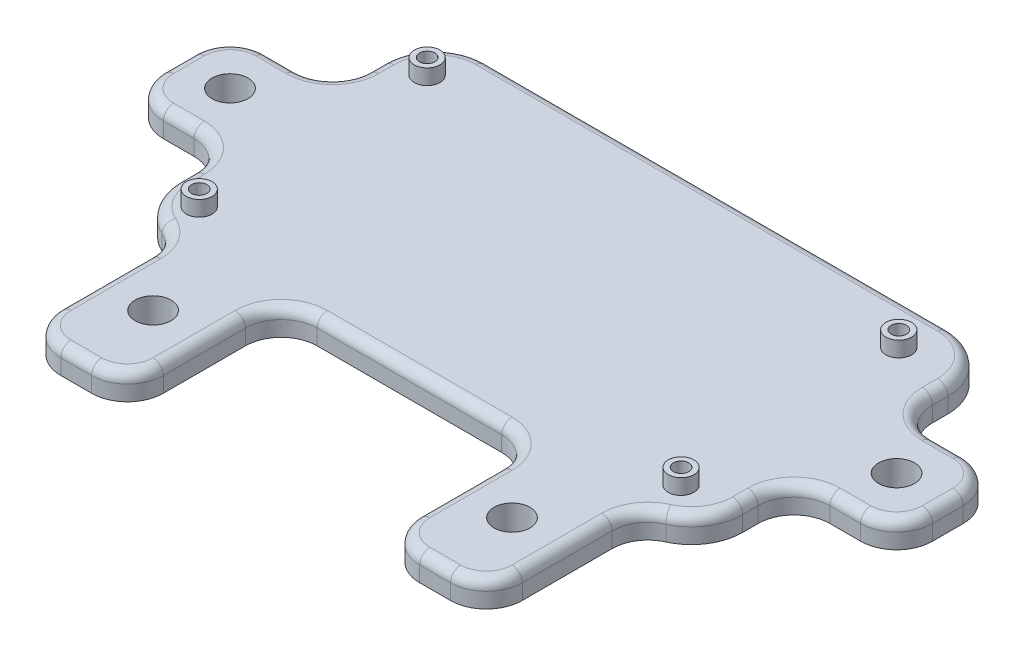
SolidWorks part; units mm, degrees
ref_plane "Front Plane" through (0, 0, 0) normal (0, 0, 1) x (1, 0, 0)
ref_plane "Top Plane" through (0, 0, 0) normal (0, 1, 0) x (1, 0, 0)
ref_plane "Right Plane" through (0, 0, 0) normal (1, 0, 0) x (0, 0, -1)
sketch "Sketch1" plane through (0, 0, 0) normal (0, 1, 0) x (1, 0, 0)
  line L1 (-49.43, 40.0745) -> (60.57, 40.0745)
  line L2 (-49.43, 40.0745) -> (-49.43, -19.9255)
  line L3 (-49.43, -19.9255) -> (60.57, -19.9255)
  line L4 (60.57, 40.0745) -> (60.57, -19.9255)
  dimension "D1" = 60
  dimension "D2" = 110
extrude "Boss-Extrude1" add sketch "Sketch1" along normal blind 5
sketch "Sketch2" plane through (0, 5, 0) normal (0, 1, 0) x (1, 0, 0)
  line L0 (-49.43, -19.9255) -> (60.57, -19.9255) construction
  line L1 (-49.43, 40.0745) -> (-49.43, -19.9255) construction
  circle A0 centre (-42.43, 31.5245) radius 1.0922
  circle A1 centre (-42.43, -12.9255) radius 1.0922
  circle A2 centre (51.55, -12.9255) radius 1.0922
  circle A3 centre (49.55, 31.5245) radius 1.0922
  dimension "D4" = 2.1844
  dimension "D5" = 93.98
  dimension "D1" = 44.45
  dimension "D2" = 7
  dimension "D3" = 7
extrude "Cut-Extrude1" cut sketch "Sketch2" against normal blind 10
sketch "Sketch3" plane through (0, 5, 0) normal (0, 1, 0) x (1, 0, 0)
  circle A0 centre (-42.43, 31.5245) radius 2.5
  circle A1 centre (-42.43, -12.9255) radius 2.5
  circle A2 centre (51.55, -12.9255) radius 2.5
  circle A3 centre (49.55, 31.5245) radius 2.5
  dimension "D1" = 5
extrude "Boss-Extrude2" add sketch "Sketch3" along normal blind 3
sketch "Sketch4" plane through (0, 8, 0) normal (0, 1, 0) x (1, 0, 0)
  circle A0 centre (-42.43, 31.5245) radius 1.5
  circle A1 centre (49.55, 31.5245) radius 1.5
  circle A2 centre (51.55, -12.9255) radius 1.5
  circle A3 centre (-42.43, -12.9255) radius 1.5
  dimension "D1" = 3
extrude "Cut-Extrude2" cut sketch "Sketch4" against normal blind 3
sketch "Sketch5" plane through (60.57, 0, 0) normal (1, 0, 0) x (0, 0, -1)
  line L0 (10.0745, 5) -> (10.0745, 0) construction
  line L1 (-19.9255, 5) -> (40.0745, 5) construction
  line L2 (-19.9255, 0) -> (40.0745, 0) construction
  line L4 (0.0745, 5) -> (20.0745, 5)
  line L5 (0.0745, 5) -> (0.0745, 0)
  line L6 (0.0745, 0) -> (20.0745, 0)
  line L7 (20.0745, 5) -> (20.0745, 0)
  line L8 (0.0745, 5) -> (20.0745, 0) construction
  line L9 (0.0745, 0) -> (20.0745, 5) construction
  point P6 (10.0745, 2.5)
  dimension "D1" = 20
extrude "Boss-Extrude3" add sketch "Sketch5" along normal blind 20 and the other way blind 130
sketch "Sketch6" plane through (0, 5, 0) normal (0, 1, 0) x (1, 0, 0)
  line L0 (-69.43, 10.0745) -> (80.57, 10.0745) construction
  line L1 (-69.43, 20.0745) -> (-69.43, 0.0745) construction
  line L2 (80.57, 20.0745) -> (80.57, 0.0745) construction
  circle A0 centre (-59.43, 10.0745) radius 3.5
  circle A1 centre (70.57, 10.0745) radius 3.5
  dimension "D3" = 7
  dimension "D1" = 10
  dimension "D2" = 10
extrude "Cut-Extrude3" cut sketch "Sketch6" against normal blind 20
sketch "Sketch7" plane through (0, 0, 19.9255) normal (0, 0, 1) x (1, 0, 0)
  line L0 (-49.43, 2.5) -> (60.57, 2.5) construction
  line L1 (-49.43, 5) -> (-49.43, 0) construction
  line L2 (60.57, 5) -> (60.57, 0) construction
  line L3 (5.57, 5) -> (5.57, 0) construction
  line L4 (-49.43, 5) -> (60.57, 5) construction
  line L5 (-49.43, 0) -> (60.57, 0) construction
  line L7 (-39.43, 5) -> (-19.43, 5)
  line L8 (-39.43, 5) -> (-39.43, 0)
  line L9 (-39.43, 0) -> (-19.43, 0)
  line L10 (-19.43, 5) -> (-19.43, 0)
  line L11 (-39.43, 5) -> (-19.43, 0) construction
  line L12 (-39.43, 0) -> (-19.43, 5) construction
  line L13 (30.57, 5) -> (50.57, 5)
  line L14 (30.57, 5) -> (30.57, 0)
  line L15 (30.57, 0) -> (50.57, 0)
  line L16 (50.57, 5) -> (50.57, 0)
  line L17 (30.57, 5) -> (50.57, 0) construction
  line L18 (30.57, 0) -> (50.57, 5) construction
  point P12 (-29.43, 2.5)
  point P17 (40.57, 2.5)
  dimension "D1" = 20
  dimension "D2" = 20
  dimension "D3" = 35
  dimension "D4" = 35
extrude "Boss-Extrude4" add sketch "Sketch7" along normal blind 30
sketch "Sketch8" plane through (0, 5, 0) normal (0, 1, 0) x (1, 0, 0)
  line L0 (50.57, -34.9255) -> (-39.43, -34.9255) construction
  line L1 (50.57, -49.9255) -> (50.57, -19.9255) construction
  line L2 (-39.43, -49.9255) -> (-39.43, -19.9255) construction
  line L3 (-29.43, -49.9255) -> (-29.43, -5.7984) construction
  line L4 (-19.43, -49.9255) -> (-39.43, -49.9255) construction
  line L5 (40.57, -49.9255) -> (40.57, -1.6081) construction
  line L6 (50.57, -49.9255) -> (30.57, -49.9255) construction
  circle A0 centre (-29.43, -34.9255) radius 3.5
  circle A1 centre (40.57, -34.9255) radius 3.5
  dimension "D1" = 7
extrude "Cut-Extrude4" cut sketch "Sketch8" against normal blind 30
fillet "Fillet1" radius 10 4 edges at (-49.43, 2.5, 19.9255) (-49.43, 2.5, -40.0745) (60.57, 2.5, -40.0745) (60.57, 2.5, 19.9255)
fillet "Fillet2" radius 7 8 edges at (60.57, 2.5, -20.0745) (60.57, 2.5, -0.0745) (-49.43, 2.5, -0.0745) (-49.43, 2.5, -20.0745) (-69.43, 2.5, -20.0745) (-69.43, 2.5, -0.0745) (80.57, 2.5, -20.0745) (80.57, 2.5, -0.0745)
fillet "Fillet3" radius 7 8 edges at (30.57, 2.5, 19.9255) (50.57, 2.5, 19.9255) (50.57, 2.5, 49.9255) (30.57, 2.5, 49.9255) (-19.43, 2.5, 49.9255) (-39.43, 2.5, 49.9255)
fillet "Fillet4" radius 2 38 edges at (-17.3797, 5, 21.9757) (-21.4802, 5, 47.8752) (-29.43, 5, 49.9255) (-37.3797, 5, 47.8752) (-40.5488, 5, 21.6211) (-49.43, 5, 8.4255) (-51.4802, 5, 1.9757) (-59.43, 5, -0.0745) (-67.3797, 5, -2.1248) (-69.43, 5, -10.0745) (-67.3797, 5, -18.0243) (-59.43, 5, -20.0745) (-51.4802, 5, -22.1248) (-49.43, 5, -28.5745) (-46.501, 5, -37.1456) (5.57, 5, -40.0745) (57.6411, 5, -37.1456) (60.57, 5, -28.5745) (62.6203, 5, -22.1248) (70.57, 5, -20.0745) (78.5198, 5, -18.0243) (80.57, 5, -10.0745) (78.5198, 5, -2.1248) (70.57, 5, -0.0745) (62.6203, 5, 1.9757) (60.57, 5, 8.4255) (58.9717, 5, 15.3488) (51.6889, 5, 21.6211) (50.57, 5, 34.1715) (48.5198, 5, 47.8752) (40.57, 5, 49.9255) (32.6203, 5, 47.8752) (30.57, 5, 34.9255) (28.5198, 5, 21.9757)
